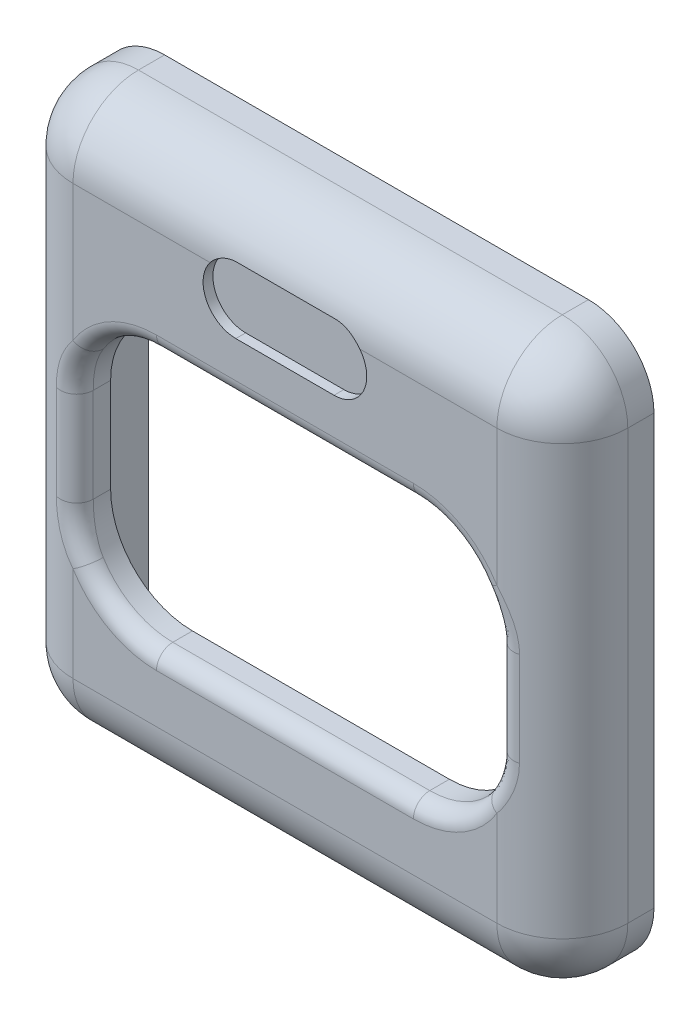
SolidWorks part; units mm, degrees
ref_plane "Спереди" through (0, 0, 0) normal (0, 0, 1) x (1, 0, 0)
ref_plane "Сверху" through (0, 0, 0) normal (0, 1, 0) x (1, 0, 0)
ref_plane "Справа" through (0, 0, 0) normal (1, 0, 0) x (0, 0, -1)
sketch "Эскиз1" plane through (0, 0, 0) normal (0, 0, 1) x (1, 0, 0)
  line L0 (-34.25, -43.4059) -> (-61.75, -43.4059) construction
  line L1 (-34.25, -43.4059) -> (-34.25, -15.6059) construction
  line L2 (-61.75, -43.4059) -> (-61.75, -15.6059) construction
  line L3 (-34.25, -15.6059) -> (-61.75, -15.6059) construction
  line L6 (-55.3, -15.6059) -> (-61.75, -15.6059) construction
  line L7 (-34.05, -43.6059) -> (-61.95, -43.6059)
  line L8 (-61.95, -43.6059) -> (-61.95, -15.4059)
  line L9 (-34.05, -15.4059) -> (-61.95, -15.4059)
  line L10 (-34.05, -43.6059) -> (-34.05, -15.4059)
  line L11 (-31.05, -12.4059) -> (-64.95, -12.4059)
  line L12 (-64.95, -46.6059) -> (-64.95, -12.4059)
  line L13 (-31.05, -46.6059) -> (-64.95, -46.6059)
  line L14 (-31.05, -46.6059) -> (-31.05, -12.4059)
  point P0 (-61.75, -14.0366)
  dimension "D1" = 0.2
  dimension "D2" = 3
extrude "Бобышка-Вытянуть1" add sketch "Эскиз1" along normal blind 4
sketch "Эскиз2" plane through (0, 0, 4) normal (0, 0, 1) x (1, 0, 0)
  line L0 (-61.35, -22.3759) -> (-61.35, -39.1359) construction
  line L1 (-34.65, -22.3759) -> (-61.35, -22.3759) construction
  line L2 (-34.65, -39.1359) -> (-34.65, -22.3759) construction
  line L3 (-61.35, -39.1359) -> (-34.65, -39.1359) construction
  line L4 (-60.85, -27.8759) -> (-60.85, -33.6359)
  line L5 (-55.85, -38.6359) -> (-40.15, -38.6359)
  line L6 (-35.15, -33.6359) -> (-35.15, -27.8759)
  line L7 (-40.15, -22.8759) -> (-55.85, -22.8759)
  line L12 (-61.35, -22.3759) -> (-61.35, -39.1359) construction
  line L13 (-34.65, -22.3759) -> (-61.35, -22.3759) construction
  line L14 (-34.65, -39.1359) -> (-34.65, -22.3759) construction
  line L15 (-61.35, -39.1359) -> (-34.65, -39.1359) construction
  line L16 (-60.85, -22.8759) -> (-60.85, -38.6359) construction
  line L17 (-60.85, -38.6359) -> (-35.15, -38.6359) construction
  line L18 (-35.15, -22.8759) -> (-60.85, -22.8759) construction
  line L19 (-35.15, -38.6359) -> (-35.15, -22.8759) construction
  line L24 (-31.05, -46.6059) -> (-31.05, -12.4059)
  line L25 (-31.05, -12.4059) -> (-64.95, -12.4059)
  line L26 (-64.95, -12.4059) -> (-64.95, -46.6059)
  line L27 (-64.95, -46.6059) -> (-31.05, -46.6059)
  line L28 (-31.05, -46.6059) -> (-31.05, -12.4059)
  line L29 (-31.05, -12.4059) -> (-64.95, -12.4059)
  line L30 (-64.95, -12.4059) -> (-64.95, -46.6059)
  line L31 (-64.95, -46.6059) -> (-31.05, -46.6059)
  arc A0 (-60.85, -33.6359) -> (-55.85, -38.6359) centre (-55.85, -33.6359) ccw
  arc A1 (-60.85, -27.8759) -> (-55.85, -22.8759) centre (-55.85, -27.8759) cw
  arc A2 (-35.15, -27.8759) -> (-40.15, -22.8759) centre (-40.15, -27.8759) ccw
  arc A3 (-40.15, -38.6359) -> (-35.15, -33.6359) centre (-40.15, -33.6359) ccw
  point P22 (-60.7932, -27.9327)
  dimension "D2" = 5
  dimension "D1" = 0.5
  dimension "D3" = 0
extrude "Бобышка-Вытянуть2" add sketch "Эскиз2" against normal up to surface (2.2 mm away)
fillet "Скругление1" radius 4 4 edges at (-31.05, -12.4059, 2) (-31.05, -46.6059, 2) (-64.95, -46.6059, 2) (-64.95, -12.4059, 2)
sketch "Эскиз3" plane through (0, 0, 4) normal (0, 0, 1) x (1, 0, 0)
  line L0 (-48, -22.8759) -> (-48, -12.4059) construction
  line L1 (-40.15, -22.8759) -> (-55.85, -22.8759) construction
  line L2 (-35.05, -12.4059) -> (-60.95, -12.4059) construction
  line L3 (-45, -17.6409) -> (-51, -17.6409) construction
  line L4 (-45, -19.6409) -> (-51, -19.6409)
  line L5 (-45, -15.6409) -> (-51, -15.6409)
  arc A0 (-45, -19.6409) -> (-45, -15.6409) centre (-45, -17.6409) ccw
  arc A1 (-51, -15.6409) -> (-51, -19.6409) centre (-51, -17.6409) ccw
  point P8 (-48, -17.6409)
  dimension "D2" = 2
  dimension "D1" = 6
extrude "Вырез-Вытянуть1" cut sketch "Эскиз3" against normal blind 0.6
fillet "Скругление2" radius 4 8 edges at (-32.2216, -45.4343, 4) (-48, -46.6059, 4) (-63.7784, -45.4343, 4) (-64.95, -29.5059, 4) (-63.7784, -13.5775, 4) (-48, -12.4059, 4) (-32.2216, -13.5775, 4) (-31.05, -29.5059, 4)
sketch "Эскиз4" plane through (0, 0, 0) normal (0, 0, -1) x (-1, 0, 0)
  line L5 (34.05, -15.4059) -> (34.05, -43.6059)
  line L6 (61.95, -15.4059) -> (34.05, -15.4059)
  line L7 (61.95, -43.6059) -> (61.95, -15.4059)
  line L12 (34.05, -43.6059) -> (61.95, -43.6059)
  line L13 (34.05, -15.4059) -> (34.05, -43.6059)
  line L14 (61.95, -15.4059) -> (34.05, -15.4059)
  line L15 (61.95, -43.6059) -> (61.95, -15.4059)
  line L16 (34.05, -43.6059) -> (61.95, -43.6059)
  line L17 (60.95, -12.4059) -> (35.05, -12.4059)
  line L18 (31.05, -16.4059) -> (31.05, -42.6059)
  line L19 (35.05, -46.6059) -> (60.95, -46.6059)
  line L20 (64.95, -42.6059) -> (64.95, -16.4059)
  line L21 (60.95, -12.4059) -> (35.05, -12.4059)
  line L22 (31.05, -16.4059) -> (31.05, -42.6059)
  line L23 (35.05, -46.6059) -> (60.95, -46.6059)
  line L24 (64.95, -42.6059) -> (64.95, -16.4059)
  arc A12 (35.05, -12.4059) -> (31.05, -16.4059) centre (35.05, -16.4059) ccw
  arc A13 (31.05, -42.6059) -> (35.05, -46.6059) centre (35.05, -42.6059) ccw
  arc A14 (60.95, -46.6059) -> (64.95, -42.6059) centre (60.95, -42.6059) ccw
  arc A15 (64.95, -16.4059) -> (60.95, -12.4059) centre (60.95, -16.4059) ccw
  arc A16 (35.05, -12.4059) -> (31.05, -16.4059) centre (35.05, -16.4059) ccw
  arc A17 (31.05, -42.6059) -> (35.05, -46.6059) centre (35.05, -42.6059) ccw
  arc A18 (60.95, -46.6059) -> (64.95, -42.6059) centre (60.95, -42.6059) ccw
  arc A19 (64.95, -16.4059) -> (60.95, -12.4059) centre (60.95, -16.4059) ccw
  dimension "D1" = 0
  dimension "D2" = 0
extrude "Бобышка-Вытянуть3" add sketch "Эскиз4" along normal blind 1.6
fillet "Скругление3" radius 1 8 edges at (-59.3855, -37.1714, 4) (-60.85, -30.7559, 4) (-59.3855, -24.3404, 4) (-48, -22.8759, 4) (-36.6145, -24.3404, 4) (-35.15, -30.7559, 4) (-36.6145, -37.1714, 4) (-48, -38.6359, 4)
